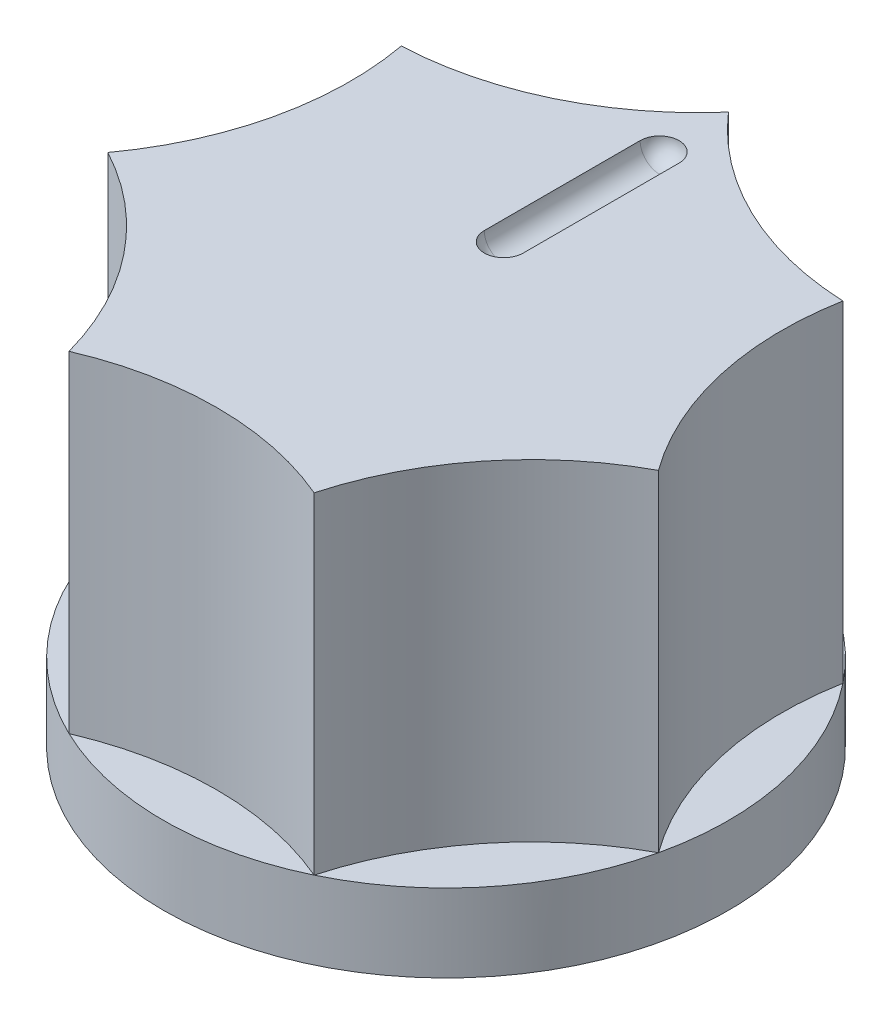
SolidWorks part; units mm, degrees
ref_plane "Front Plane" through (0, 0, 0) normal (0, 0, 1) x (1, 0, 0)
ref_plane "Top Plane" through (0, 0, 0) normal (0, 1, 0) x (1, 0, 0)
ref_plane "Right Plane" through (0, 0, 0) normal (1, 0, 0) x (0, 0, -1)
sketch "Sketch1" plane through (0, 0, 0) normal (0, 1, 0) x (1, 0, 0)
  circle A0 centre (0, 0) radius 7.25
extrude "Boss-Extrude1" add sketch "Sketch1" along normal blind 2
sketch "Sketch2" plane through (0, 2, 0) normal (0, 1, 0) x (1, 0, 0)
  line L1 (0, 7.25) -> (-5.6683, 4.5203) construction
  line L2 (-5.6683, 4.5203) -> (-7.0682, -1.6133) construction
  line L3 (-7.0682, -1.6133) -> (-3.1457, -6.532) construction
  line L4 (-3.1457, -6.532) -> (3.1457, -6.532) construction
  line L5 (3.1457, -6.532) -> (7.0682, -1.6133) construction
  line L6 (7.0682, -1.6133) -> (5.6683, 4.5203) construction
  line L7 (5.6683, 4.5203) -> (0, 7.25) construction
  line L8 (0, 6.532) -> (-5.1069, 4.0727) construction
  line L9 (-5.1069, 4.0727) -> (-6.3683, -1.4535) construction
  line L10 (-6.3683, -1.4535) -> (-2.8341, -5.8852) construction
  line L11 (-2.8341, -5.8852) -> (2.8341, -5.8852) construction
  line L12 (2.8341, -5.8852) -> (6.3683, -1.4535) construction
  line L13 (6.3683, -1.4535) -> (5.1069, 4.0727) construction
  line L14 (5.1069, 4.0727) -> (0, 6.532) construction
  circle A0 centre (0, 0) radius 6.532 construction
  circle A1 centre (0, 0) radius 6.532 construction
  arc A2 (0, 7.25) -> (5.6683, 4.5203) centre (6.0123, 12.4848) ccw
  arc A3 (5.6683, 4.5203) -> (7.0682, -1.6133) centre (13.5096, 3.0835) ccw
  arc A4 (7.0682, -1.6133) -> (3.1457, -6.532) centre (10.8339, -8.6397) ccw
  arc A5 (3.1457, -6.532) -> (-3.1457, -6.532) centre (0, -13.857) ccw
  arc A6 (-3.1457, -6.532) -> (-7.0682, -1.6133) centre (-10.8339, -8.6397) ccw
  arc A7 (-7.0682, -1.6133) -> (-5.6683, 4.5203) centre (-13.5096, 3.0835) ccw
  arc A8 (-5.6683, 4.5203) -> (0, 7.25) centre (-6.0123, 12.4848) ccw
  point P40 (0, 0)
  dimension "D1" = 7
extrude "Boss-Extrude2" add sketch "Sketch2" along normal blind 8.5
sketch "Sketch3" plane through (0, 10.5, 0) normal (0, 1, 0) x (1, 0, 0)
  line L0 (0, 5.4828) -> (0, 1.4828) construction
  line L1 (0.5, 5.4828) -> (0.5, 1.4828)
  line L2 (-0.5, 5.4828) -> (-0.5, 1.4828)
  arc A0 (0.5, 5.4828) -> (-0.5, 5.4828) centre (0, 5.4828) ccw
  arc A1 (-0.5, 1.4828) -> (0.5, 1.4828) centre (0, 1.4828) ccw
  point P3 (0, 3.4828)
  dimension "D1" = 1
extrude "Indicator" cut sketch "Sketch3" against normal blind 0.5
fillet "Fillet1" radius 0.5 4 edges at (0.5, 10, -3.4828) (0, 10, -0.9828) (-0.5, 10, -3.4828) (0, 10, -5.9828)
sketch "Sketch4" plane through (0, 0, 0) normal (0, -1, 0) x (-1, 0, 0)
  circle A0 centre (0, 0) radius 3
  dimension "D1" = 6
extrude "Cut-Extrude2" cut sketch "Sketch4" against normal blind 8
chamfer "Chamfer1" distance 0.5 angle 45 1 edges at (0, 0, -3)
